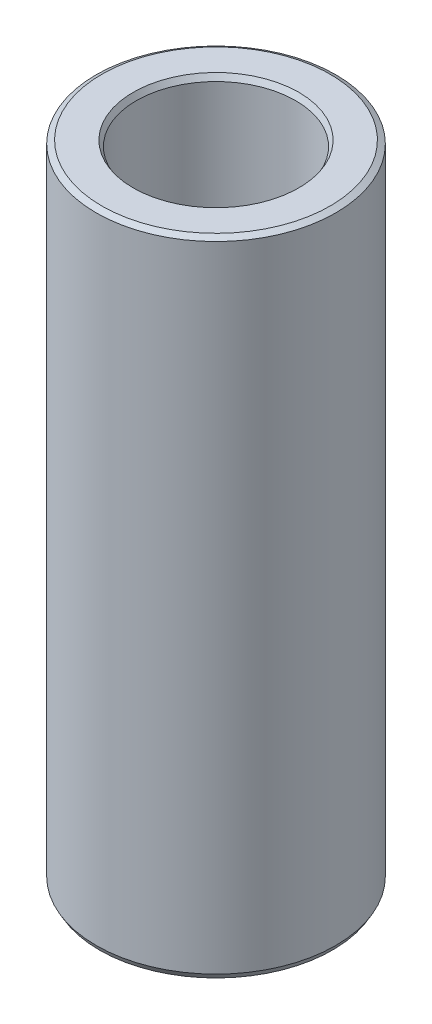
SolidWorks part; units mm, degrees
ref_plane "Front Plane" through (0, 0, 0) normal (0, 0, 1) x (1, 0, 0)
ref_plane "Top Plane" through (0, 0, 0) normal (0, 1, 0) x (1, 0, 0)
ref_plane "Right Plane" through (0, 0, 0) normal (1, 0, 0) x (0, 0, -1)
sketch "Sketch1" plane through (0, 0, 0) normal (0, 1, 0) x (1, 0, 0)
  circle A0 centre (0, 0) radius 25
  dimension "SLEEVE_OD" = 50
extrude "Boss-Extrude1" add sketch "Sketch1" along normal blind 134.2698
sketch "Sketch2" plane through (0, 0, 0) normal (0, 1, 0) x (1, 0, 0)
  circle A0 centre (0, 0) radius 16.6271
  dimension "BORE_D" = 33.2542
extrude "Cut-Extrude1" cut sketch "Sketch2" along normal through all
chamfer "Chamfer1" distance 0.6643 angle 60.335 4 edges at (0, 134.2698, 16.6271) (0, 0, 16.6271) (0, 0, 25) (0, 134.2698, 25) first distance on face at (0, 134.2698, 16.6271) first distance on face at (0, 0, 16.6271) first distance on face at (0, 134.2698, 25)
